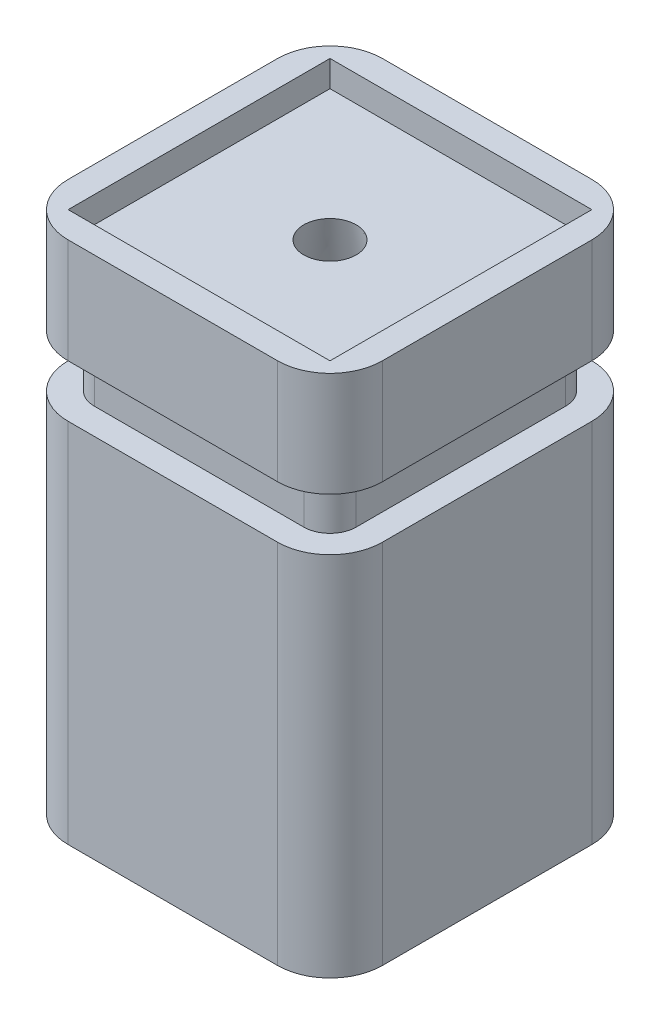
SolidWorks part; units mm, degrees
ref_plane "Front Plane" through (0, 0, 0) normal (0, 0, 1) x (1, 0, 0)
ref_plane "Top Plane" through (0, 0, 0) normal (0, 1, 0) x (1, 0, 0)
ref_plane "Right Plane" through (0, 0, 0) normal (1, 0, 0) x (0, 0, -1)
sketch "Sketch2" plane through (0, 0, 0) normal (0, 1, 0) x (1, 0, 0)
  line L1 (-15, -15) -> (15, -15)
  line L2 (-15, -15) -> (-15, 15)
  line L3 (-15, 15) -> (15, 15)
  line L4 (15, -15) -> (15, 15)
  line L5 (0, 15) -> (0, -15) construction
  line L6 (-15, 0) -> (15, 0) construction
  point P0 (0, 0)
  dimension "D1" = 30
  dimension "D2" = 30
extrude "Boss-Extrude1" add sketch "Sketch2" along normal blind 50
sketch "Sketch3" plane through (0, 50, 0) normal (0, 1, 0) x (1, 0, 0)
  line L1 (-12.5, -12.5) -> (12.5, -12.5)
  line L2 (-12.5, -12.5) -> (-12.5, 12.5)
  line L3 (-12.5, 12.5) -> (12.5, 12.5)
  line L4 (12.5, -12.5) -> (12.5, 12.5)
  line L5 (0, 12.5) -> (0, -12.5) construction
  line L6 (-12.5, 0) -> (12.5, 0) construction
  point P0 (0, 0)
  dimension "D1" = 25
  dimension "D2" = 25
extrude "Cut-Extrude1" cut sketch "Sketch3" against normal blind 2.5
fillet "Fillet1" radius 5 4 edges at (15, 25, 15) (15, 25, -15) (-15, 25, -15) (-15, 25, 15)
sketch "Sketch6" plane through (0, 0, 0) normal (0, -1, 0) x (1, 0, 0)
  circle A0 centre (0, 0) radius 12.5
  dimension "D1" = 25
sketch "Sketch8" plane through (0, 47.5, 0) normal (0, 1, 0) x (1, 0, 0)
  circle A0 centre (0, 0) radius 2.5
  dimension "D1" = 5
loft "Cut-Loft2" cut profiles "Sketch6", "Sketch8" connector at (0, 0, -12.5) connector at (0.7845, 47.5, -2.3737)
ref_plane "Plane1" through (0, 35, 0) normal (0, 1, 0) x (1, 0, 0)
sketch "Sketch9" plane through (0, 35, 0) normal (0, 1, 0) x (1, 0, 0)
  line L8 (12.5, -10) -> (12.5, 10)
  line L9 (10, 12.5) -> (-10, 12.5)
  line L10 (-12.5, 10) -> (-12.5, -10)
  line L11 (-10, -12.5) -> (10, -12.5)
  line L12 (12.5, -10) -> (12.5, 10)
  line L13 (10, 12.5) -> (-10, 12.5)
  line L14 (-12.5, 10) -> (-12.5, -10)
  line L15 (-10, -12.5) -> (10, -12.5)
  circle A1 centre (0, 0) radius 19.953
  arc A10 (12.5, 10) -> (10, 12.5) centre (10, 10) ccw
  arc A11 (-10, 12.5) -> (-12.5, 10) centre (-10, 10) ccw
  arc A12 (-12.5, -10) -> (-10, -12.5) centre (-10, -10) ccw
  arc A13 (10, -12.5) -> (12.5, -10) centre (10, -10) ccw
  arc A14 (12.5, 10) -> (10, 12.5) centre (10, 10) ccw
  arc A15 (-10, 12.5) -> (-12.5, 10) centre (-10, 10) ccw
  arc A16 (-12.5, -10) -> (-10, -12.5) centre (-10, -10) ccw
  arc A17 (10, -12.5) -> (12.5, -10) centre (10, -10) ccw
  dimension "D2" = 2.5
extrude "Cut-Extrude2" cut sketch "Sketch9" along normal blind 5
